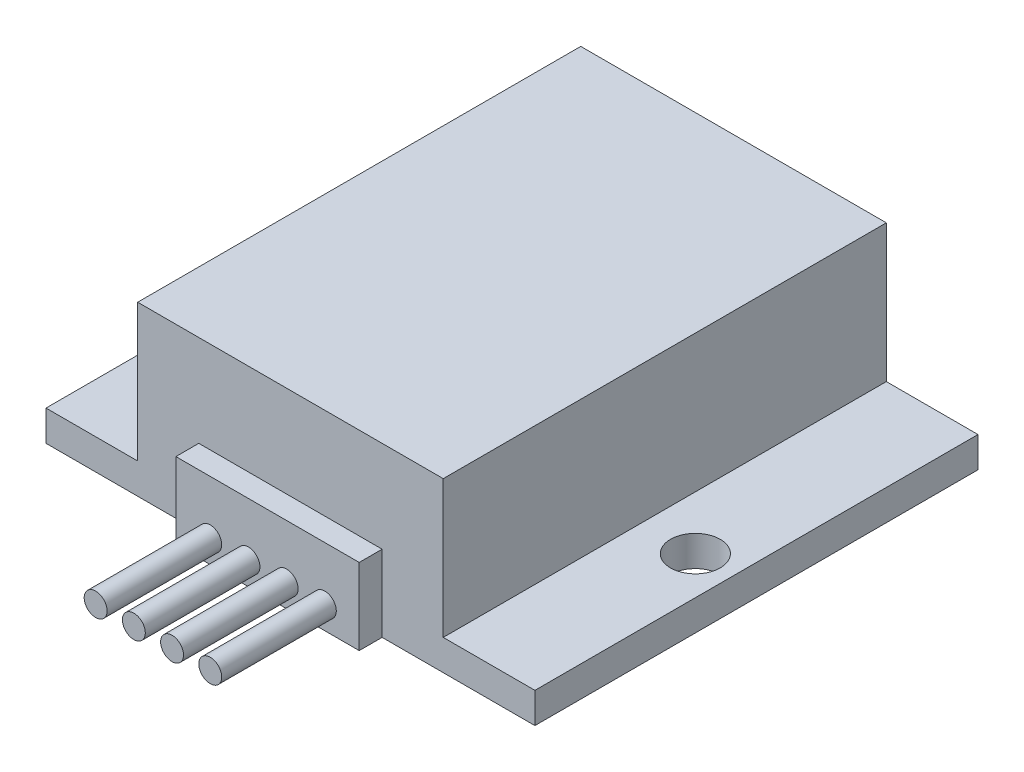
SolidWorks part; units mm, degrees
ref_plane "Front Plane" through (0, 0, 0) normal (0, 0, 1) x (1, 0, 0)
ref_plane "Top Plane" through (0, 0, 0) normal (0, 1, 0) x (1, 0, 0)
ref_plane "Right Plane" through (0, 0, 0) normal (1, 0, 0) x (0, 0, -1)
ref_axis "X" through (-88.99, 0, 0) along (1, 0, 0)
ref_axis "Y" through (0, 55, 0) along (0, -1, 0)
ref_axis "Z" through (0, 0, -88.99) along (0, 0, 1)
sketch "Sketch1" plane through (0, 0, 0) normal (0, 1, 0) x (1, 0, 0)
  line L0 (27, -3) -> (27, -29) construction
  line L1 (-32, 29) -> (32, 29)
  line L2 (-32, 29) -> (-32, -29)
  line L3 (-32, -29) -> (32, -29)
  line L4 (32, 29) -> (32, -29)
  line L5 (-32, 29) -> (32, -29) construction
  line L6 (-32, -29) -> (32, 29) construction
  line L7 (27, -3) -> (32, -3) construction
  line L8 (0, 29) -> (0, -29) construction
  line L9 (-12, -29) -> (-12, -32)
  line L10 (-12, -32) -> (12, -32)
  line L11 (12, -32) -> (12, -29)
  line L12 (0, -29) -> (0, -32) construction
  line L13 (-20, 29) -> (-20, -29)
  line L14 (20, 29) -> (20, -29)
  line L15 (-20, 0) -> (0, 0) construction
  line L16 (0, 0) -> (20, 0) construction
  circle A0 centre (27, -3) radius 3.25
  circle A2 centre (-27, -3) radius 3.25
  point P0 (0, 0)
  dimension "D3" = 26
  dimension "D5" = 6.5
  dimension "D1" = 58
  dimension "D2" = 64
  dimension "D4" = 5
  dimension "D6" = 24
  dimension "D7" = 3
  dimension "D8" = 40
extrude "Boss-Extrude1" add sketch "Sketch1" along normal blind 4 contours L13 L1 L2 L3 A2 | L1 L14 L3 L4 A0 region at (-25.9499, 0, -0.1502) region at (25.9499, 0, -0.1502)
extrude "Boss-Extrude2" add sketch "Sketch1<3>" along normal blind 22 contours L14 L1 L13 L3 region at (0, 0, 0)
sketch "Sketch1<3>" plane through (0, 0, 0) normal (0, 1, 0) x (1, 0, 0) same geometry as "Sketch1"
extrude "Boss-Extrude3" add sketch "Sketch1<4>" along normal blind 10 contours L10 L11 L3 L9 region at (0, 0, 30.5)
sketch "Sketch1<4>" plane through (0, 0, 0) normal (0, 1, 0) x (1, 0, 0) same geometry as "Sketch1"
sketch "Sketch2" plane through (0, 0, 32) normal (0, 0, 1) x (1, 0, 0)
  line L0 (-7.5, 3) -> (-2.5, 3) construction
  line L1 (-2.5, 3) -> (2.5, 3) construction
  line L2 (2.5, 3) -> (7.5, 3) construction
  line L3 (0, 3) -> (0, 0) construction
  line L4 (-12, 0) -> (12, 0) construction
  circle A0 centre (-7.5, 3) radius 1.5
  circle A1 centre (-2.5, 3) radius 1.5
  circle A2 centre (2.5, 3) radius 1.5
  circle A3 centre (7.5, 3) radius 1.5
  dimension "D1" = 3
  dimension "D2" = 5
  dimension "D3" = 3
extrude "Boss-Extrude4" add sketch "Sketch2" along normal blind 15
